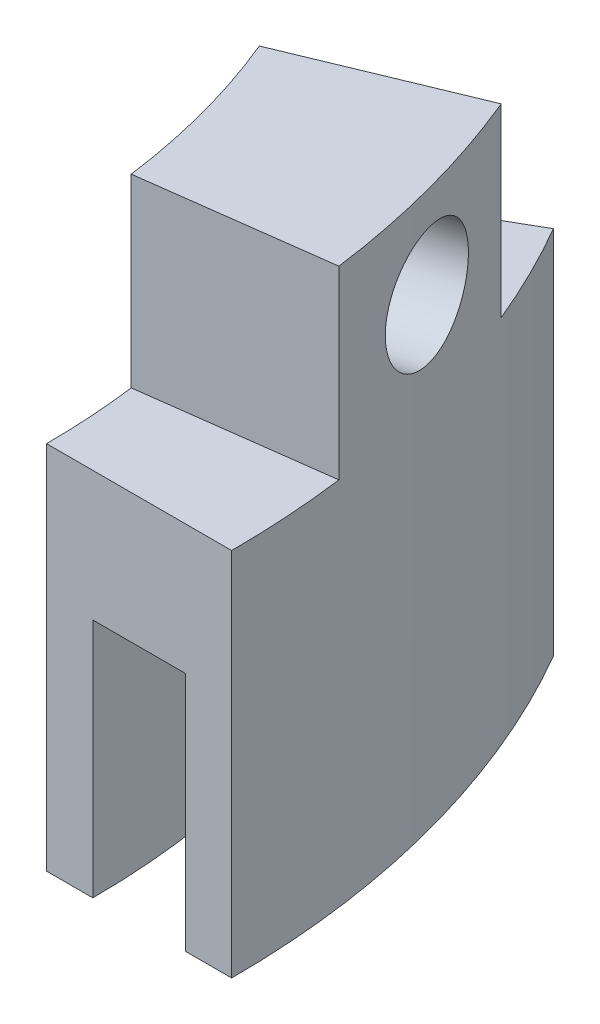
SolidWorks part; units mm, degrees
ref_plane "Front Plane" through (0, 0, 0) normal (0, 0, 1) x (1, 0, 0)
ref_plane "Top Plane" through (0, 0, 0) normal (0, 1, 0) x (1, 0, 0)
ref_plane "Right Plane" through (0, 0, 0) normal (1, 0, 0) x (0, 0, -1)
sketch "Sketch3" plane through (0, 0, 0) normal (0, 1, 0) x (1, 0, 0)
  line L0 (0, 0) -> (37.5, 0) construction
  line L1 (37.5, 0) -> (47.5, 0)
  line L2 (32.476, 18.75) -> (41.1362, 23.75)
  arc A0 (37.5, 0) -> (32.476, 18.75) centre (0, 0) ccw
  arc A1 (47.5, 0) -> (41.1362, 23.75) centre (0, 0) ccw
  dimension "D2" = 37.5
  dimension "D3" = 30
  dimension "D1" = 10
extrude "Boss-Extrude1" add sketch "Sketch3" along normal blind 30
sketch "Sketch4" plane through (0, 0, 0) normal (0, 1, 0) x (1, 0, 0)
  line L0 (37.5, 0) -> (47.5, 0) construction
  line L1 (41.1362, 23.75) -> (32.476, 18.75) construction
  line L2 (34.641, 20) -> (38.9711, 22.5)
  line L3 (40, 0) -> (45, 0)
  arc A0 (40, 0) -> (34.641, 20) centre (0, 0) ccw
  arc A1 (45, 0) -> (38.9711, 22.5) centre (0, 0) ccw
  dimension "D2" = 40
  dimension "D1" = 5
extrude "Cut-Extrude1" cut sketch "Sketch4" along normal blind 13
sketch "Sketch5" plane through (0, 30, 0) normal (0, 1, 0) x (1, 0, 0)
  line L0 (0, 0) -> (45.8815, 12.2939) construction
  line L2 (41.1362, 23.75) -> (32.476, 18.75) construction
  line L8 (41.1362, 23.75) -> (32.476, 18.75)
  line L9 (0, 0) -> (43.8843, 18.1775) construction
  line L10 (43.8843, 18.1775) -> (34.6455, 14.3506)
  arc A0 (47.5, 0) -> (41.1362, 23.75) centre (0, 0) ccw construction
  arc A1 (37.5, 0) -> (32.476, 18.75) centre (0, 0) ccw construction
  arc A10 (34.6455, 14.3506) -> (32.476, 18.75) centre (0, 0) ccw
  arc A11 (43.8843, 18.1775) -> (41.1362, 23.75) centre (0, 0) ccw
  dimension "D1" = 7.5
extrude "Cut-Extrude2" cut sketch "Sketch5" against normal blind 10
ref_plane "Plane1" through (0, 0, 0) normal (0.2588, 0, 0.9659) x (0.9659, 0, -0.2588)
mirror "Mirror1" about plane through (0, 0, 0) normal (0.2588, 0, 0.9659) of "Cut-Extrude2"
ref_plane "Plane2" through (45.8815, 0, -12.2939) normal (0.9659, 0, -0.2588) x (-0.2588, 0, -0.9659)
sketch "Sketch6" plane through (45.8815, 0, -12.2939) normal (0.9659, 0, -0.2588) x (-0.2588, 0, -0.9659)
  line L0 (-6.2, 30) -> (6.2, 20) construction
  circle A0 centre (0, 25) radius 3.175
  dimension "D1" = 6.35
extrude "Cut-Extrude3" cut sketch "Sketch6" against normal through all
ref_axis "CenterAxis" through (0, 30, 0) along (0, -1, 0)
